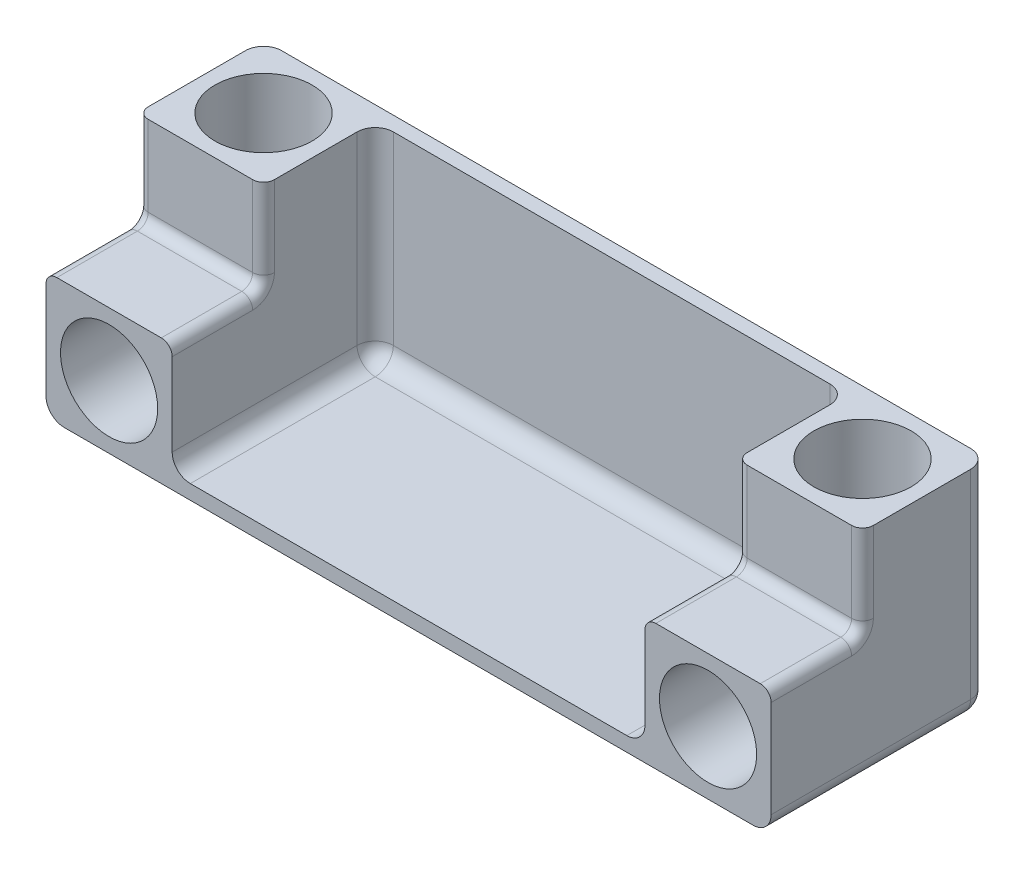
SolidWorks part; units mm, degrees
ref_plane "Front Plane" through (0, 0, 0) normal (0, 0, 1) x (1, 0, 0)
ref_plane "Top Plane" through (0, 0, 0) normal (0, 1, 0) x (1, 0, 0)
ref_plane "Right Plane" through (0, 0, 0) normal (1, 0, 0) x (0, 0, -1)
sketch "Sketch1" plane through (0, 0, 0) normal (0, 1, 0) x (1, 0, 0)
  line L0 (-65.2, 44.6799) -> (-65.2, -11.3201)
  line L1 (0, -11.3201) -> (-100, -11.3201)
  line L2 (0, -11.3201) -> (0, 48.6799)
  line L3 (0, 48.6799) -> (-100, 48.6799)
  line L4 (-100, -11.3201) -> (-100, 48.6799)
  line L5 (-65.2, 44.6799) -> (0, 44.6799)
  circle A0 centre (-82.6, 31.2799) radius 13.4
  dimension "D3" = 17.4
  dimension "D4" = 17.4
  dimension "D5" = 26.8
  dimension "D1" = 100
  dimension "D2" = 60
  dimension "D6" = 34.8
  dimension "D7" = 4
extrude "Boss-Extrude1" add sketch "Sketch1" along normal blind 56 contours L0 L5 L2 L3 L4 L1 A0 region at (-75.2934, 0, -18.789)
sketch "Sketch2" plane through (0, 0, 0) normal (0, 1, 0) x (1, 0, 0)
  line L1 (0, 48.6799) -> (-100, 48.6799)
  line L2 (0, 48.6799) -> (0, -11.3201)
  line L3 (0, -11.3201) -> (-100, -11.3201)
  line L4 (-100, 48.6799) -> (-100, -11.3201)
extrude "Boss-Extrude2" add sketch "Sketch2" against normal blind 4
sketch "Sketch3" plane through (0, 0, 11.3201) normal (0, 0, 1) x (1, 0, 0)
  line L0 (-100, 56) -> (-100, -4) construction
  line L2 (-100, -4) -> (0, -4) construction
  circle A0 centre (-82.6, 13.4) radius 13.4
  dimension "D2" = 17.4
  dimension "D3" = 26.8
  dimension "D1" = 17.4
extrude "Cut-Extrude1" cut sketch "Sketch3" against normal blind 25.2 contours A0
sketch "Sketch4" plane through (-100, 0, 0) normal (-1, 0, 0) x (0, 0, 1)
  line L0 (-48.6799, -4) -> (11.3201, -4) construction
  line L9 (11.3201, 56) -> (-13.8799, 56)
  line L10 (11.3201, 56) -> (11.3201, 30.8)
  line L11 (11.3201, 30.8) -> (-13.8799, 30.8)
  line L12 (-13.8799, 56) -> (-13.8799, 30.8)
  line L13 (-48.6799, 56) -> (-48.6799, -4) construction
  dimension "D1" = 34.8
  dimension "D3" = 34.8
extrude "Cut-Extrude2" cut sketch "Sketch4" against normal blind 51.2
sketch3d "3DSketch1"
  line L0 (0, 56, -44.6799) -> (0, 0, -44.6799) construction
  line L1 (0, 0, -44.6799) -> (0, 0, 11.3201) construction
ref_plane "Plane1" through (0, 0, 0) normal (-1, 0, 0) x (0, 0, 1)
mirror "Mirror2" about plane through (0, 0, 0) normal (-1, 0, 0) of "Cut-Extrude1", "Boss-Extrude2", "Boss-Extrude1", "Cut-Extrude2"
fillet "Fillet1" radius 5 5 edges at (65.2, 0, -16.6799) (65.2, 28, -44.6799) (-65.2, 0, -16.6799) (0, 0, -44.6799) (-65.2, 28, -44.6799)
fillet "Fillet2" radius 5 5 edges at (-100, -4, -18.6799) (-100, 26, -48.6799) (100, -4, -18.6799) (0, -4, -48.6799) (100, 26, -48.6799)
fillet "Fillet4" radius 3 5 edges at (-65.2, 30.8, -1.2799) (-100, 30.8, -1.2799) (-82.6, 30.8, -13.8799) (-100, 43.4, -13.8799) (-65.2, 43.4, -13.8799)
fillet "Fillet5" radius 3 5 edges at (100, 30.8, -1.2799) (65.2, 30.8, -1.2799) (100, 43.4, -13.8799) (65.2, 43.4, -13.8799) (82.6, 30.8, -13.8799)
